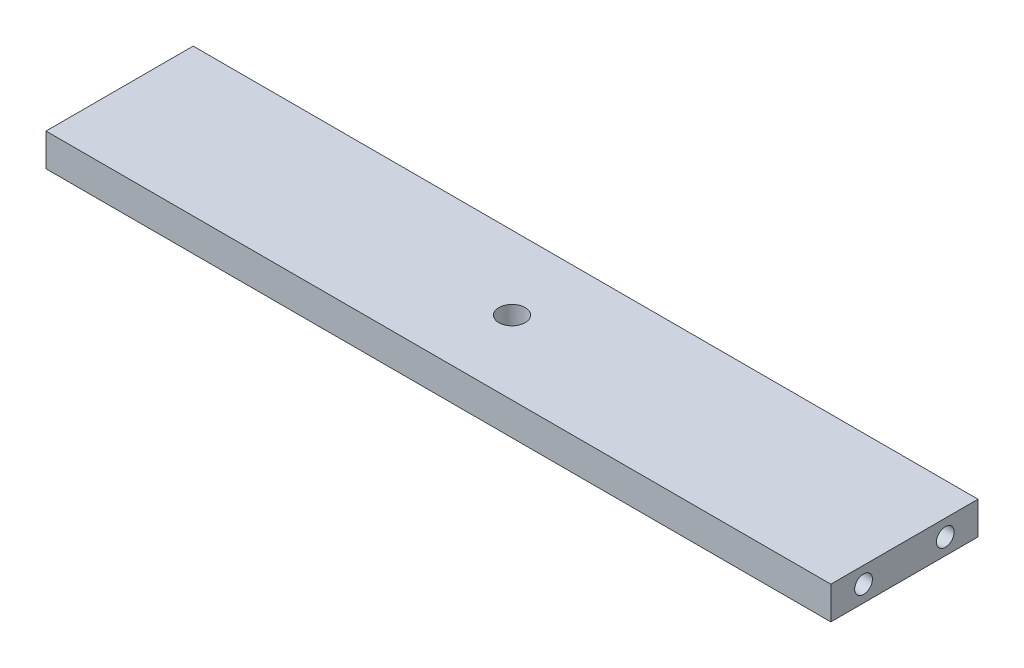
SolidWorks part; units mm, degrees
material "6061 Alloy"
ref_plane "Front Plane" through (0, 0, 0) normal (0, 0, 1) x (1, 0, 0)
ref_plane "Top Plane" through (0, 0, 0) normal (0, 1, 0) x (1, 0, 0)
ref_plane "Right Plane" through (0, 0, 0) normal (1, 0, 0) x (0, 0, -1)
sketch "Sketch2" plane through (0, 0, 0) normal (0, 1, 0) x (1, 0, 0)
  line L1 (-76.2, -14.2875) -> (76.2, -14.2875)
  line L2 (-76.2, -14.2875) -> (-76.2, 14.2875)
  line L3 (-76.2, 14.2875) -> (76.2, 14.2875)
  line L4 (76.2, -14.2875) -> (76.2, 14.2875)
  line L5 (-76.2, -14.2875) -> (76.2, 14.2875) construction
  line L6 (-76.2, 14.2875) -> (76.2, -14.2875) construction
  point P0 (0, 0)
  dimension "D1" = 152.4
  dimension "D2" = 28.575
extrude "Boss-Extrude1" add sketch "Sketch2" along normal blind 6.35
hole_wizard "1/4-20 Tapped Hole1" positions "Sketch4" profile "Sketch5" tap size "1/4-20" standard "ANSI Inch" end condition through all
sketch "Sketch4" plane through (0, 0, 0) normal (0, -1, 0) x (-1, 0, 0)
  point P0 (0, 0)
sketch "Sketch5" plane through (0, 0, 0) normal (1, 0, 0) x (0, 0, -1)
  line L0 (0, 0) -> (0, 6.35)
  line L1 (0, 6.35) -> (2.5527, 6.35)
  line L2 (2.5527, 6.35) -> (2.5527, 0)
  line L5 (2.5527, 0) -> (0, 0)
  line L11 (0, -6.35) -> (0, 107.95) construction
  dimension "Thru Tap Drill Dia." = 5.1054
  dimension "Thru Tap Drill Depth" = 6.35
cosmetic thread "Hole Thread1" parameters "D2"=6.35
hole_wizard "#8-32 Tapped Hole1" positions "Sketch6" profile "Sketch7" tap size "#8-32" standard "ANSI Inch"
sketch "Sketch6" plane through (-76.2, 0, 0) normal (-1, 0, 0) x (0, 0, 1)
  line L0 (-14.2875, 6.35) -> (-14.2875, 0) construction
  line L1 (14.2875, 6.35) -> (14.2875, 0) construction
  line L2 (-14.2875, 0) -> (14.2875, 0) construction
  point P0 (-7.9375, 3.175)
  point P2 (7.9375, 3.175)
  dimension "D1" = 6.35
  dimension "D2" = 6.35
  dimension "D3" = 3.175
  dimension "D4" = 3.175
sketch "Sketch7" plane through (-76.2, 3.175, -7.9375) normal (0, 1, 0) x (0, 0, 1)
  line L0 (0, 0) -> (0, 7.3878)
  line L1 (0, 7.3878) -> (1.7272, 6.35)
  line L2 (1.7272, 6.35) -> (1.7272, 0)
  line L5 (1.7272, 0) -> (0, 0)
  line L10 (0, 7.3878) -> (-1.7272, 6.35) construction
  line L11 (0, -6.35) -> (0, 107.95) construction
  dimension "Tap Drill Dia." = 3.4544
  dimension "Tap Drill Depth" = 6.35
  dimension "Drill Angle" = 118
cosmetic thread "Hole Thread2" parameters "D1"=6.35, "D2"=4.1656
cosmetic thread "Hole Thread3" parameters "D1"=6.35, "D2"=4.1656
mirror "Mirror1" about plane through (0, 0, 0) normal (1, 0, 0) of "#8-32 Tapped Hole1"
